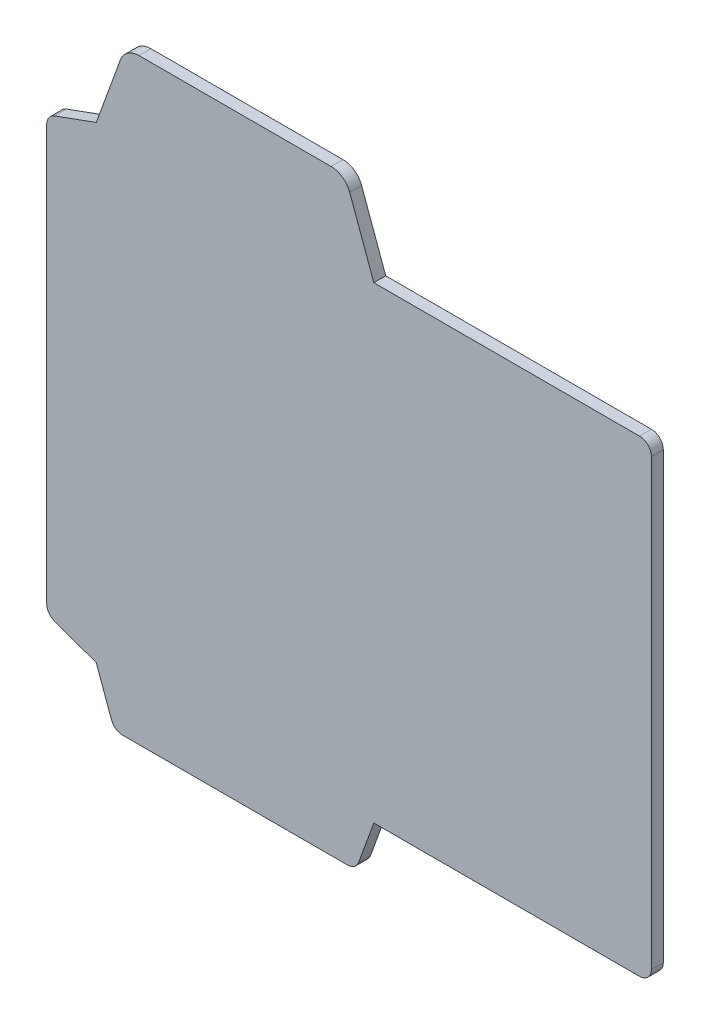
SolidWorks part; units mm, degrees
ref_plane "Front" through (0, 0, 0) normal (0, 0, 1) x (1, 0, 0)
ref_plane "Top" through (0, 0, 0) normal (0, 1, 0) x (1, 0, 0)
ref_plane "Right" through (0, 0, 0) normal (1, 0, 0) x (0, 0, -1)
sketch "Esquisse1" plane through (0, 0, 0) normal (0, 0, 1) x (1, 0, 0)
  line L1 (0, 0) -> (70, 0)
  line L2 (0, 0) -> (0, 118)
  line L3 (0, 118) -> (70, 118)
  line L4 (70, 0) -> (70, 118)
  dimension "D1" = 70
  dimension "D2" = 118
extrude "Boss.-Extru.1" add sketch "Esquisse1" along normal blind 3
sketch "Esquisse2" plane through (0, 0, 3) normal (0, 0, 1) x (1, 0, 0)
  line L0 (0, 0) -> (-12.5, 4.5496)
  line L1 (-12.5, 4.5496) -> (-12.5, 113.4504)
  line L2 (-12.5, 59) -> (0, 59) construction
  line L3 (0, 118) -> (0, 0) construction
  line L4 (0, 118) -> (-12.5, 113.4504)
  line L5 (35, 0) -> (35, -12.5) construction
  line L6 (0, 0) -> (70, 0) construction
  line L7 (65.4504, -12.5) -> (4.5496, -12.5)
  line L8 (4.5496, -12.5) -> (0, 0)
  line L9 (65.4504, -12.5) -> (70, 0)
  line L10 (70, 0) -> (0, 0)
  line L11 (0, 0) -> (0, 118)
  line L12 (70, 118) -> (62.7206, 138)
  line L13 (70, 118) -> (0, 118) construction
  line L14 (70, 0) -> (70, 118) construction
  line L15 (62.7206, 138) -> (7.2794, 138)
  line L16 (35, 138) -> (35, 118) construction
  line L17 (0, 118) -> (7.2794, 138)
  line L18 (0, 118) -> (70, 118)
  line M10 (0, 118) -> (0, 0)
  line M11 (0, 0) -> (70, 0)
  line M13 (70, 118) -> (0, 118)
  dimension "D1" = 12.5
  dimension "D2" = 70
  dimension "D3" = 70
  dimension "D4" = 20
  dimension "D5" = 70
extrude "Boss.-Extru.2" add sketch "Esquisse2" against normal up to vertex (3 mm away) contours L17 L12 L15 M13 | L4 L1 L0 M10 | L7 L9 L8 M11 region at (35, 127.6131, 3) region at (35, -6.1052, 3) region at (-6.1665, 59, 3) up to point (70, 118, 0)
fillet "Congé1" radius 3 2 edges at (-12.5, 4.5496, 1.5) (-12.5, 113.4504, 1.5)
fillet "Congé2" radius 3 2 edges at (65.4504, -12.5, 1.5) (4.5496, -12.5, 1.5)
fillet "Congé3" radius 5 2 edges at (7.2794, 138, 1.5) (62.7206, 138, 1.5)
sketch "Esquisse3" plane through (0, 0, 3) normal (0, 0, 1) x (1, 0, 0)
  line L1 (70, 0) -> (140, 0)
  line L2 (70, 0) -> (70, 118)
  line L3 (70, 118) -> (140, 118)
  line L4 (140, 0) -> (140, 118)
  line L5 (70, 0) -> (70, 118) construction
  dimension "D1" = 70
extrude "Boss.-Extru.3" add sketch "Esquisse3" against normal up to vertex (3 mm away) up to point (70, 118, 0)
fillet "Congé4" radius 3 2 edges at (140, 0, 1.5) (140, 118, 1.5)
